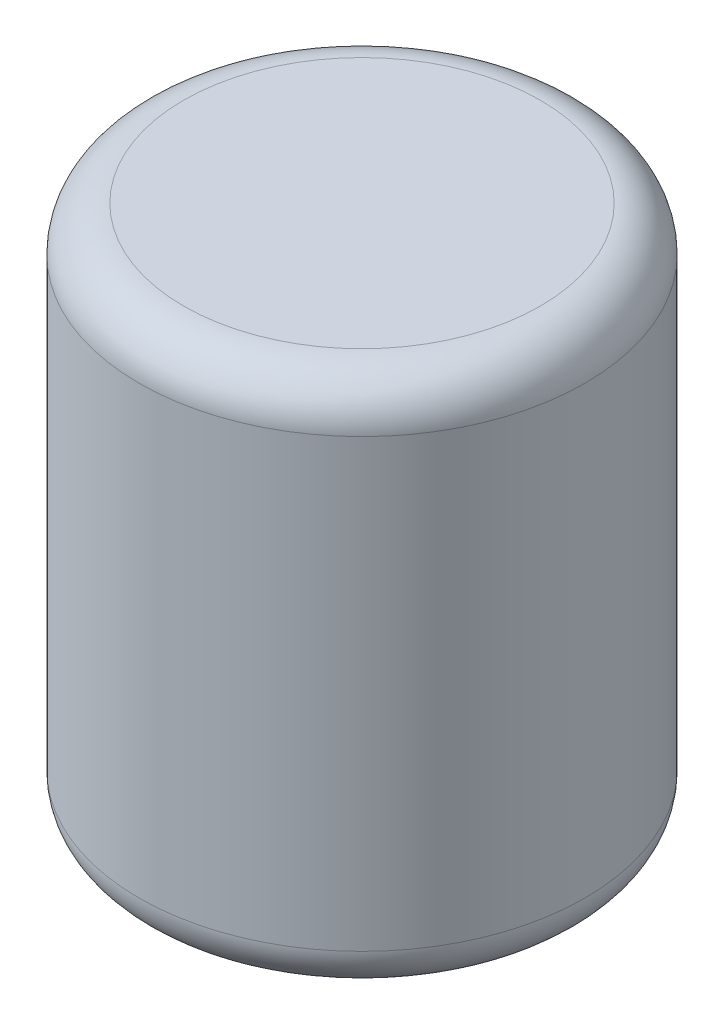
SolidWorks part; units mm, degrees
material "Silicon"
ref_plane "Front Plane" through (0, 0, 0) normal (0, 0, 1) x (1, 0, 0)
ref_plane "Top Plane" through (0, 0, 0) normal (0, 1, 0) x (1, 0, 0)
ref_plane "Right Plane" through (0, 0, 0) normal (1, 0, 0) x (0, 0, -1)
sketch "Sketch2" plane through (0, 0, 0) normal (0, 1, 0) x (1, 0, 0)
  circle A0 centre (0, 0) radius 63.5
  dimension "D1" = 127
extrude "Boss-Extrude1" add sketch "Sketch2" along normal blind 152.4
fillet "Fillet1" radius 12.7 2 edges at (0, 0, 63.5) (0, 152.4, 63.5)
equation "\"PackedDiameter\"= 5"
equation "\"PackedLength\"= 6"
equation "\"D1@Sketch2\"=\"PackedDiameter\""
equation "\"D1@Boss-Extrude1\"=\"PackedLength\""
